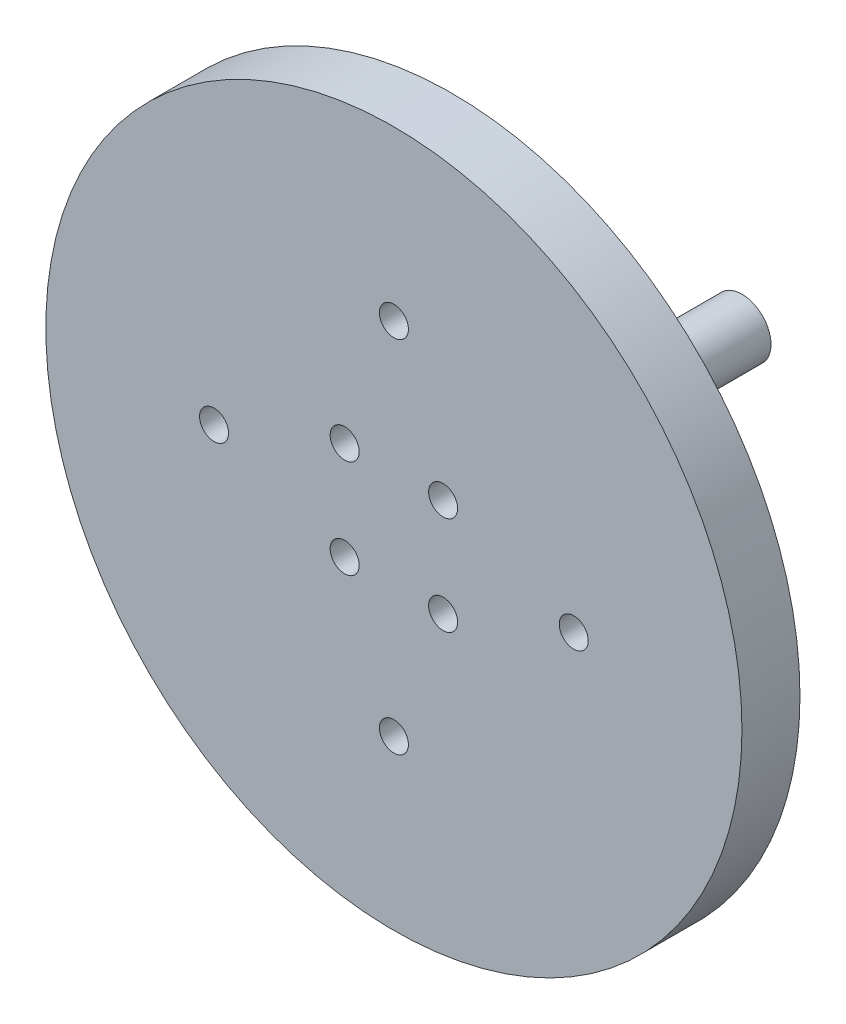
SolidWorks part; units mm, degrees
ref_plane "Front Plane" through (0, 0, 0) normal (0, 0, 1) x (1, 0, 0)
ref_plane "Top Plane" through (0, 0, 0) normal (0, 1, 0) x (1, 0, 0)
ref_plane "Right Plane" through (0, 0, 0) normal (1, 0, 0) x (0, 0, -1)
sketch "Sketch1" plane through (0, 0, 0) normal (0, 0, 1) x (1, 0, 0)
  circle A0 centre (0, 0) radius 30
extrude "Boss-Extrude1" add sketch "Sketch1" along normal blind 5
sketch "Sketch2" plane through (0, 0, 5) normal (0, 0, 1) x (1, 0, 0)
  line L0 (0, 15.5) -> (0, 0) construction
  line L1 (0, 0) -> (4.2426, 4.2426) construction
  circle A0 centre (0, 15.5) radius 1.25
  circle A1 centre (15.5, 0) radius 1.25
  circle A2 centre (0, -15.5) radius 1.25
  circle A3 centre (-15.5, 0) radius 1.25
  circle A4 centre (4.2426, 4.2426) radius 1.25
  circle A5 centre (4.2426, -4.2426) radius 1.25
  circle A6 centre (-4.2426, -4.2426) radius 1.25
  circle A7 centre (-4.2426, 4.2426) radius 1.25
  point P5 (0, 0)
  point P12 (0, 0)
  point P21 (0, 0)
  dimension "D1" = 15.5
  dimension "D3" = 2.5
  dimension "D4" = 2.5
  dimension "D5" = 6
  dimension "D7" = 45
  dimension "D2" = 4
  dimension "D6" = 4
extrude "Cut-Extrude1" cut sketch "Sketch2" against normal blind 5
sketch "Sketch3" plane through (0, 0, 0) normal (0, 0, -1) x (-1, 0, 0)
  circle A0 centre (0, 0) radius 2.5
extrude "Boss-Extrude2" add sketch "Sketch3" along normal blind 25
